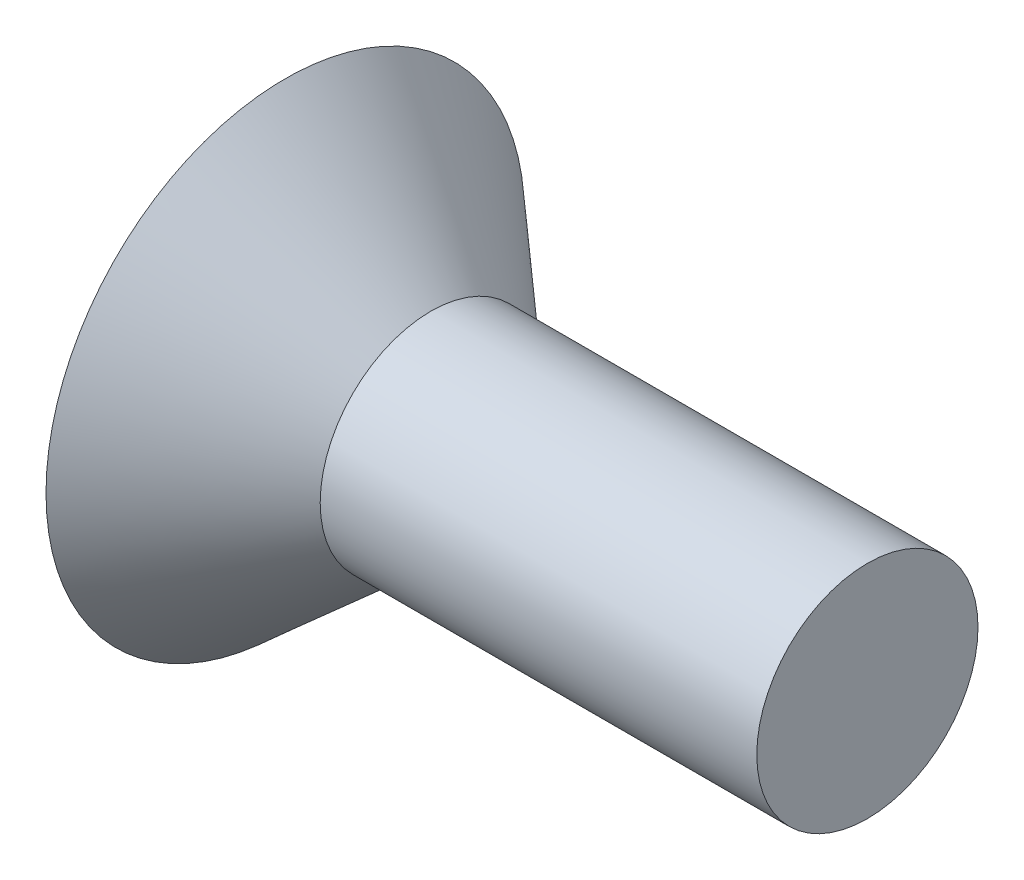
SolidWorks part; units mm, degrees
material "Alloy Steel"
ref_plane "Front Plane" through (0, 0, 0) normal (0, 0, 1) x (1, 0, 0)
ref_plane "Top Plane" through (0, 0, 0) normal (0, 1, 0) x (1, 0, 0)
ref_plane "Right Plane" through (0, 0, 0) normal (1, 0, 0) x (0, 0, -1)
sketch "Sketch1" plane through (0, 0, 0) normal (0, 0, 1) x (1, 0, 0)
  line L0 (0, 0) -> (0, 2.413)
  line L1 (0, 2.413) -> (-9.525, 2.413)
  line L2 (-9.525, 2.413) -> (-12.7, 5.2197)
  line L3 (-12.7, 5.2197) -> (-12.7, 0)
  line L4 (-12.7, 0) -> (0, 0)
  dimension "D1" = 5.2197
  dimension "D2" = 3.175
  dimension "D3" = 12.7
  dimension "D4" = 2.413
ref_axis "Axis2" through (0, 0, 0) along (-1, 0, 0)
revolve "Revolve2" add sketch "Sketch1" angle 360 about L4
sketch "Sketch2" plane through (-12.7, 0, 0) normal (-1, 0, 0) x (0, 0, 1)
  line L1 (0, 1.8331) -> (-1.5875, 0.9165)
  line L2 (-1.5875, 0.9165) -> (-1.5875, -0.9165)
  line L3 (-1.5875, -0.9165) -> (0, -1.8331)
  line L4 (0, -1.8331) -> (1.5875, -0.9165)
  line L5 (1.5875, -0.9165) -> (1.5875, 0.9165)
  line L6 (1.5875, 0.9165) -> (0, 1.8331)
  circle A0 centre (0, 0) radius 1.5875 construction
  dimension "D1" = 3.175
extrude "Cut-Extrude1" cut sketch "Sketch2" against normal blind 2.54
fillet "Fillet1" radius 0.0508 6 edges at (-12.7, -1.3748, 0.7938) (-12.7, -1.3748, -0.7937) (-12.7, 0, -1.5875) (-12.7, 1.3748, -0.7938) (-12.7, 1.3748, 0.7937) (-12.7, 0, 1.5875)
